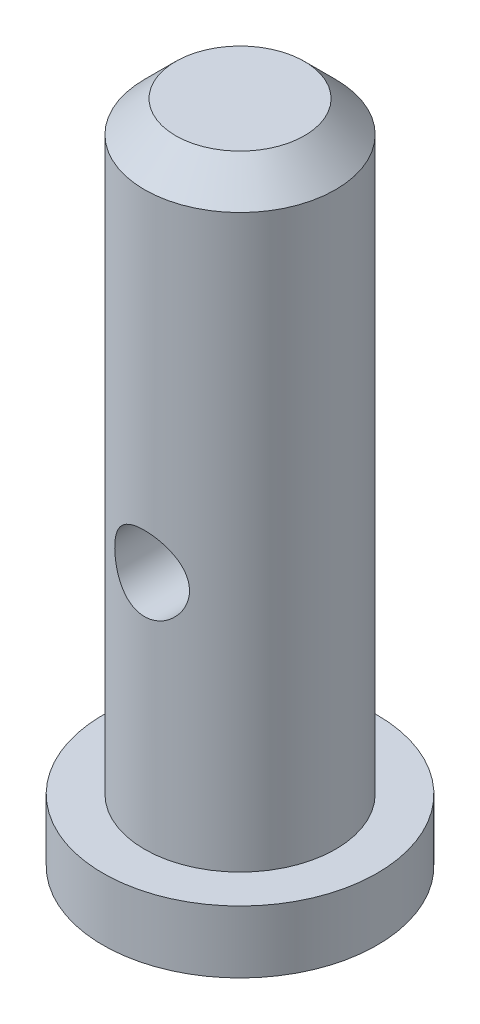
SolidWorks part; units mm, degrees
ref_plane "Front Plane" through (0, 0, 0) normal (0, 0, 1) x (1, 0, 0)
ref_plane "Top Plane" through (0, 0, 0) normal (0, 1, 0) x (1, 0, 0)
ref_plane "Right Plane" through (0, 0, 0) normal (1, 0, 0) x (0, 0, -1)
sketch "Sketch1" plane through (0, 0, 0) normal (0, 0, 1) x (1, 0, 0)
  line L0 (0, 0) -> (0, 16) construction
  line L1 (0, 16) -> (2.3, 16)
  line L2 (2.3, 16) -> (2.3, 1.5)
  line L3 (2.3, 1.5) -> (3.3, 1.5)
  line L4 (3.3, 1.5) -> (3.3, 0)
  line L5 (3.3, 0) -> (0, 0)
  line L6 (0, 0) -> (0, 16)
  dimension "D1" = 2.3
  dimension "D2" = 1.5
  dimension "D3" = 1
  dimension "D4" = 14.5
revolve "Revolve1" add sketch "Sketch1" angle 360 about L0
chamfer "Chamfer1" distance 0.75 angle 45 1 edges at (0, 16, -2.3)
sketch "Sketch2" plane through (0, 0, 0) normal (0, 0, 1) x (1, 0, 0)
  line L0 (3.3, 1.5) -> (-3.3, 1.5) construction
  circle A0 centre (0, 7.25) radius 0.9
  point P4 (-0.4625, 7.25)
  dimension "D2" = 1.8
  dimension "D1" = 5.75
extrude "Cut-Extrude1" cut sketch "Sketch2" against normal through all both and the other way through all
